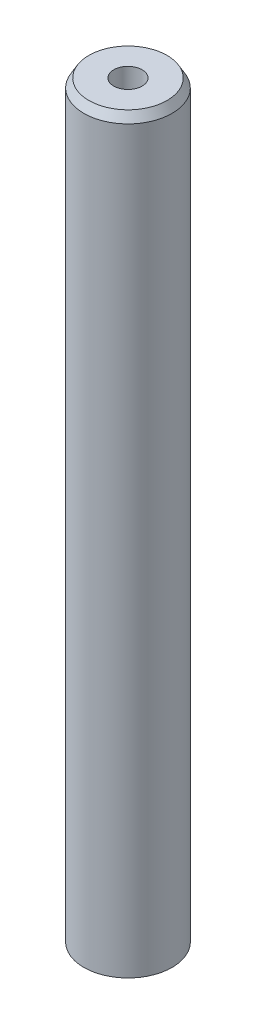
SolidWorks part; units mm, degrees
ref_plane "Front Plane" through (0, 0, 0) normal (0, 0, 1) x (1, 0, 0)
ref_plane "Top Plane" through (0, 0, 0) normal (0, 1, 0) x (1, 0, 0)
ref_plane "Right Plane" through (0, 0, 0) normal (1, 0, 0) x (0, 0, -1)
sketch "Sketch1" plane through (0, 0, 0) normal (0, 1, 0) x (1, 0, 0)
  circle A0 centre (0, 0) radius 5
  dimension "SHAFT_OD" = 10
extrude "Boss-Extrude1" add sketch "Sketch1" along normal blind 85.397
sketch "Sketch2" plane through (0, 0, 0) normal (0, 1, 0) x (1, 0, 0)
  circle A0 centre (0, 0) radius 1.6088
  dimension "BORE_D" = 3.2177
extrude "Cut-Extrude1" cut sketch "Sketch2" along normal through all
chamfer "Chamfer1" distance 0.9835 angle 30 2 edges at (0, 85.397, 5) (0, 0, 5) first distance on face at (0, 85.397, 5) first distance on face at (0, 0, 1.6088)
